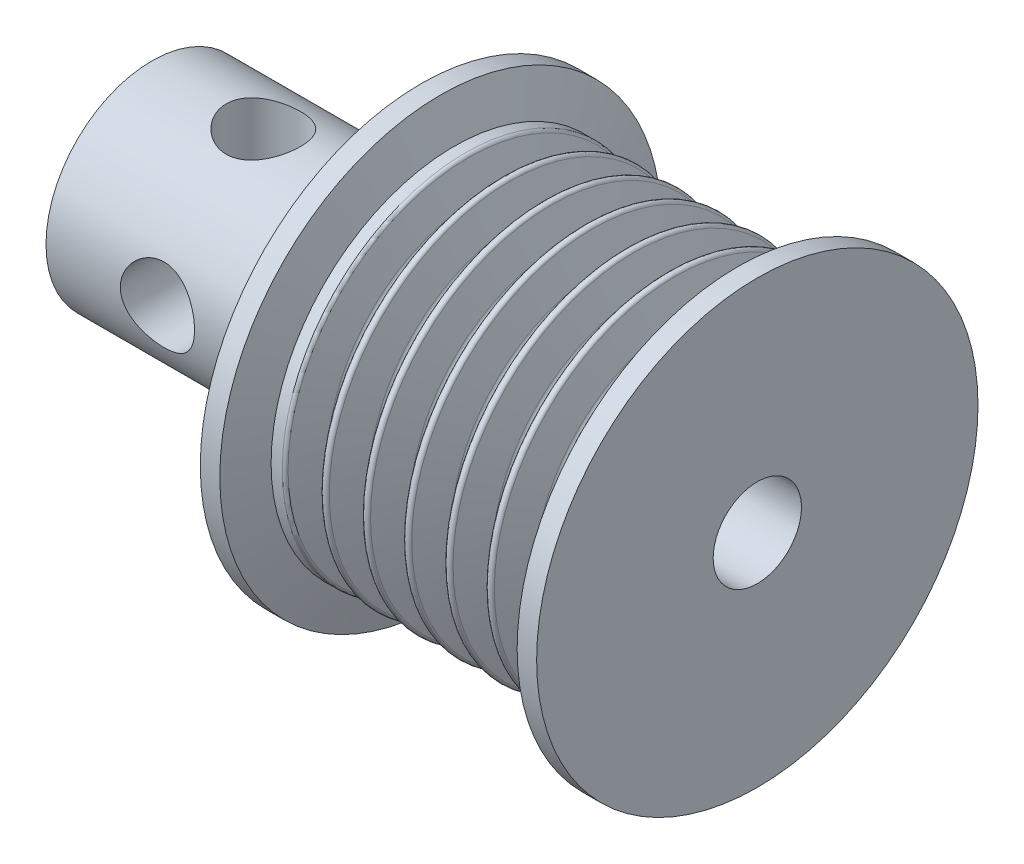
SolidWorks part; units mm, degrees
material "6061-T6 (SS)"
ref_plane "Front Plane" through (0, 0, 0) normal (0, 0, 1) x (1, 0, 0)
ref_plane "Top Plane" through (0, 0, 0) normal (0, 1, 0) x (1, 0, 0)
ref_plane "Right Plane" through (0, 0, 0) normal (1, 0, 0) x (0, 0, -1)
sketch "Sketch1" plane through (0, 0, 0) normal (0, 0, 1) x (1, 0, 0)
  line L0 (0, 0) -> (0, 2.5) construction
  line L1 (0, 2.5) -> (34.29, 2.5)
  line L2 (34.29, 2.5) -> (34.29, 12.5)
  line L3 (34.29, 12.5) -> (15.24, 12.5)
  line L4 (15.24, 12.5) -> (15.24, 6)
  line L5 (0, 0) -> (13.5959, 0) construction
  line L8 (15.24, 6) -> (0, 6)
  line L9 (0, 6) -> (0, 2.5)
  dimension "D1" = 25
  dimension "D2" = 5
  dimension "D3" = 19.05
  dimension "D6" = 12
  dimension "D7" = 15.24
revolve "Revolve1" add sketch "Sketch1" angle 360 about L5
sketch "Sketch2" plane through (0, 0, 0) normal (0, 0, 1) x (1, 0, 0)
  line L0 (29.4386, 12.5) -> (29.4386, 10.3699)
  line L1 (15.24, 6) -> (15.24, -6) construction
  line L2 (29.6295, 10.2362) -> (30.2251, 8.5999)
  line L3 (30.9889, 8.5999) -> (31.5845, 10.2362)
  line L4 (31.7754, 10.3699) -> (31.7754, 12.5)
  line L5 (31.7754, 12.5) -> (29.4386, 12.5)
  line L6 (29.4386, 11.43) -> (31.7754, 11.43) construction
  line L7 (15.24, 0) -> (34.29, 0) construction
  line L8 (29.6295, 10.2362) -> (31.5845, 10.2362) construction
  line L9 (29.4386, 12.5) -> (27.1018, 12.5) construction
  line L10 (34.29, 12.5) -> (15.24, 12.5) construction
  line L11 (27.1018, 12.5) -> (24.765, 12.5) construction
  line L13 (24.765, 0) -> (24.765, 12.5) construction
  line L15 (34.29, -12.5) -> (34.29, 12.5) construction
  arc A0 (29.4386, 10.3699) -> (29.6295, 10.2362) centre (29.4386, 10.1667) cw
  arc A1 (30.2251, 8.5999) -> (30.9889, 8.5999) centre (30.607, 8.7389) ccw
  arc A2 (31.5845, 10.2362) -> (31.7754, 10.3699) centre (31.7754, 10.1667) cw
  dimension "D1" = 0.4064
  dimension "D5" = 0.2032
  dimension "D2" = 2.3368
  dimension "D4" = 1.1938
  dimension "D6" = 40
  dimension "D7" = 11.43
revolve "Cut-Revolve1" cut sketch "Sketch2" angle 360 about L7
pattern_linear "LPattern1" count 6 spacing 2.3368 along (-1, 0, 0) of "Cut-Revolve1"
sketch "Sketch3" plane through (0, 0, 0) normal (0, 0, 1) x (1, 0, 0)
  line L0 (31.7754, 12.5) -> (33.1857, 12.5)
  line L1 (34.29, 12.5) -> (31.7754, 12.5) construction
  line L2 (33.1857, 12.5) -> (32.4104, 10.3699)
  line L3 (32.4104, 10.3699) -> (31.7754, 10.3699)
  line L4 (31.7754, 12.5) -> (31.7754, -12.5) construction
  line L5 (31.7754, 10.3699) -> (31.7754, 12.5)
  line L6 (31.7754, 10.3699) -> (31.7754, -10.3699) construction
  line L7 (30.607, 8.3325) -> (30.607, 11.4458) construction
  line L8 (24.765, 10.3699) -> (24.765, 14.7012) construction
  line L9 (17.7546, 10.3699) -> (17.7546, 12.5)
  line L10 (17.1196, 10.3699) -> (17.7546, 10.3699)
  line L11 (16.3443, 12.5) -> (17.1196, 10.3699)
  line L12 (17.7546, 12.5) -> (16.3443, 12.5)
  line L13 (0, 0) -> (26.9583, 0) construction
  arc A0 (30.2251, 8.5999) -> (30.9889, 8.5999) centre (30.607, 8.7389) ccw construction
  arc A1 (24.9559, 10.2362) -> (24.5741, 10.2362) centre (24.765, 10.1667) ccw construction
  dimension "D1" = 1.8034
  dimension "D2" = 20
revolve "Cut-Revolve2" cut sketch "Sketch3" angle 360 about L13
fillet "Fillet1" radius 0.762 1 edges at (15.24, 0, 6)
ref_plane "Plane1" through (0, 6, 0) normal (0, 1, 0) x (1, 0, 0)
sketch "Sketch6" plane through (0, 6, 0) normal (0, 1, 0) x (1, 0, 0)
  line L1 (6.311, 0) -> (0, 0) construction
  line L7 (9.74, 6) -> (9.74, -6) construction
  line L8 (14.478, 6) -> (0, 6) construction
  line L9 (0, -6) -> (14.478, -6) construction
  line L11 (15.24, 6.762) -> (15.24, -6.762) construction
  circle A0 centre (6.311, 0) radius 3.429 construction
  point P0 (6.311, 0)
  dimension "D1" = 6.858
  dimension "D2" = 5.5
hole_wizard "M5x0.8 Tapped Hole1" positions "Sketch6" profile "Sketch5" tap size "M5x0.8" standard "ANSI Metric" end condition up to next
sketch "Sketch5" plane through (6.311, 6, 0) normal (1, 0, 0) x (0, 0, 1)
  line L0 (0, 0) -> (0, 3.5)
  line L1 (0, 3.5) -> (2.1, 3.5)
  line L2 (2.1, 3.5) -> (2.1, 0)
  line L5 (2.1, 0) -> (0, 0)
  line L11 (0, -6.35) -> (0, 107.95) construction
  dimension "Thru Tap Drill Dia." = 4.2
  dimension "Thru Tap Drill Depth" = 3.5
pattern_circular "CirPattern1" count 2 over 90 about axis through (0, 0, 0) along (-1, 0, 0) of "M5x0.8 Tapped Hole1" reverse direction yes
equation "\"D2@Sketch1\"=5mm"
equation "\"D4@Sketch2\"=0.094in/2"
equation "\"D1@Sketch1\"=25mm"
equation "\"D3@Sketch1\"=0.75in"
equation "\"D7@Sketch2\"=0.9in/2"
equation "\"D7@Sketch1\"=0.60in"
equation "\"D2@Sketch6\"=5.5mm"
equation "\"D6@Sketch1\"=12mm"
